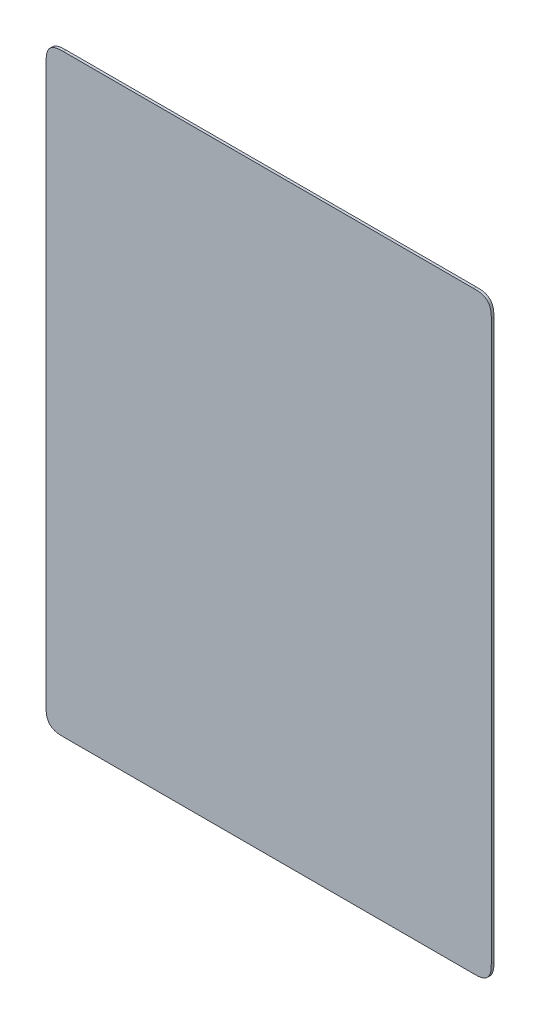
SolidWorks part; units mm, degrees
ref_plane "Front Plane" through (0, 0, 0) normal (0, 0, 1) x (1, 0, 0)
ref_plane "Top Plane" through (0, 0, 0) normal (0, 1, 0) x (1, 0, 0)
ref_plane "Right Plane" through (0, 0, 0) normal (1, 0, 0) x (0, 0, -1)
sketch "Sketch1" plane through (0, 0, 0) normal (0, 0, 1) x (1, 0, 0)
  line L1 (-255, 340) -> (255, 340)
  line L2 (-255, 340) -> (-255, -340)
  line L3 (-255, -340) -> (255, -340)
  line L4 (255, 340) -> (255, -340)
  line L5 (-255, 340) -> (255, -340) construction
  line L6 (-255, -340) -> (255, 340) construction
  point P0 (0, 0)
  dimension "D1" = 680
  dimension "D2" = 510
extrude "Boss-Extrude1" add sketch "Sketch1" along normal blind 3
fillet "Fillet1" radius 20 4 edges at (-255, 340, 1.5) (-255, -340, 1.5) (255, -340, 1.5) (255, 340, 1.5) curvature continuous yes
